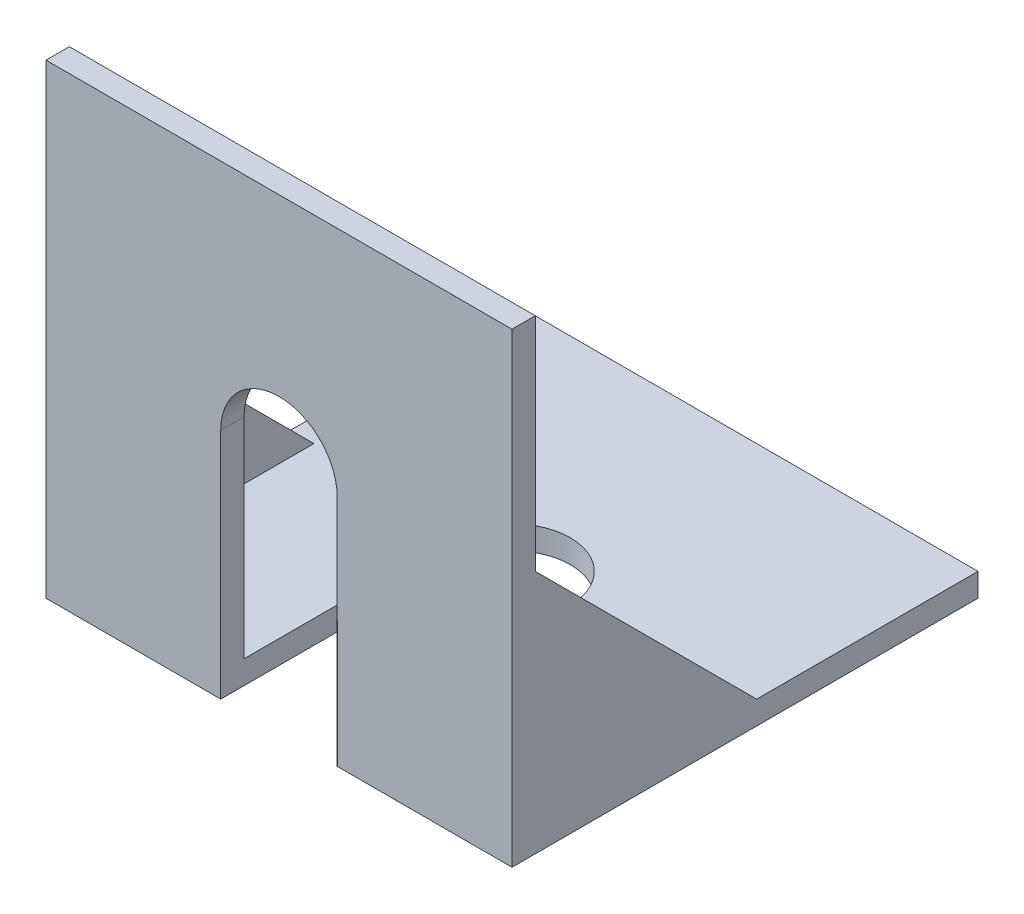
SolidWorks part; units mm, degrees
ref_plane "Front Plane" through (0, 0, 0) normal (0, 0, 1) x (1, 0, 0)
ref_plane "Top Plane" through (0, 0, 0) normal (0, 1, 0) x (1, 0, 0)
ref_plane "Right Plane" through (0, 0, 0) normal (1, 0, 0) x (0, 0, -1)
sketch "Sketch1" plane through (0, 0, 0) normal (0, 1, 0) x (1, 0, 0)
  line L1 (10, 10) -> (-10, 10)
  line L2 (10, 10) -> (10, -10)
  line L3 (10, -10) -> (-10, -10)
  line L4 (-10, 10) -> (-10, -10)
  line L5 (10, 10) -> (-10, -10) construction
  line L6 (10, -10) -> (-10, 10) construction
  circle A1 centre (0, 0) radius 2.5
  dimension "D1" = 20
  dimension "D2" = 20
extrude "Boss-Extrude1" add sketch "Sketch1" along normal blind 1
sketch "Sketch2" plane through (0, 0, 10) normal (0, 0, 1) x (1, 0, 0)
  line L1 (-10, 0) -> (10, 0)
  line L2 (-10, 0) -> (-10, 20)
  line L3 (-10, 20) -> (10, 20)
  line L4 (10, 0) -> (10, 20)
  circle A0 centre (0, 10) radius 2.5
extrude "Boss-Extrude2" add sketch "Sketch2" against normal blind 1
sketch "Sketch3" plane through (10, 0, 0) normal (1, 0, 0) x (0, 0, -1)
  line L0 (-9, 10.5) -> (0.5, 1)
  line L1 (-9, 1) -> (-9, 20) construction
  line L2 (-9, 1) -> (10, 1) construction
  line L3 (0.5, 1) -> (-9, 1)
  line L4 (-9, 1) -> (-9, 10.5)
extrude "Boss-Extrude3" add sketch "Sketch3" against normal blind 1
extrude "Boss-Extrude4" add sketch "Sketch3<2>" against normal blind 1 from offset 19 offset against normal yes
sketch "Sketch3<2>" plane through (10, 0, 0) normal (1, 0, 0) x (0, 0, -1) same geometry as "Sketch3"
sketch "Sketch4" plane through (0, 0, 9) normal (0, 0, -1) x (-1, 0, 0)
  line L0 (-2.5, 10) -> (-2.5, 0)
  line L2 (2.5, 10) -> (2.5, 0)
  line L3 (2.5, 0) -> (-2.5, 0)
  line L4 (-2.5, 10) -> (2.5, 10)
  line L5 (10, 0) -> (-10, 0) construction
  circle A0 centre (0, 10) radius 2.5 construction
sketch "Sketch5" plane through (0, 1, 0) normal (0, 1, 0) x (1, 0, 0)
  line L0 (2.5, -9) -> (2.5, 0)
  line L1 (2.5, 0) -> (-2.5, 0)
  line L2 (-2.5, 0) -> (-2.5, -9)
  line L3 (-2.5, -9) -> (2.5, -9)
  circle A0 centre (0, 0) radius 2.5 construction
extrude "Cut-Extrude1" cut sketch "Sketch5" against normal through all
extrude "Cut-Extrude2" cut sketch "Sketch4" against normal through all
